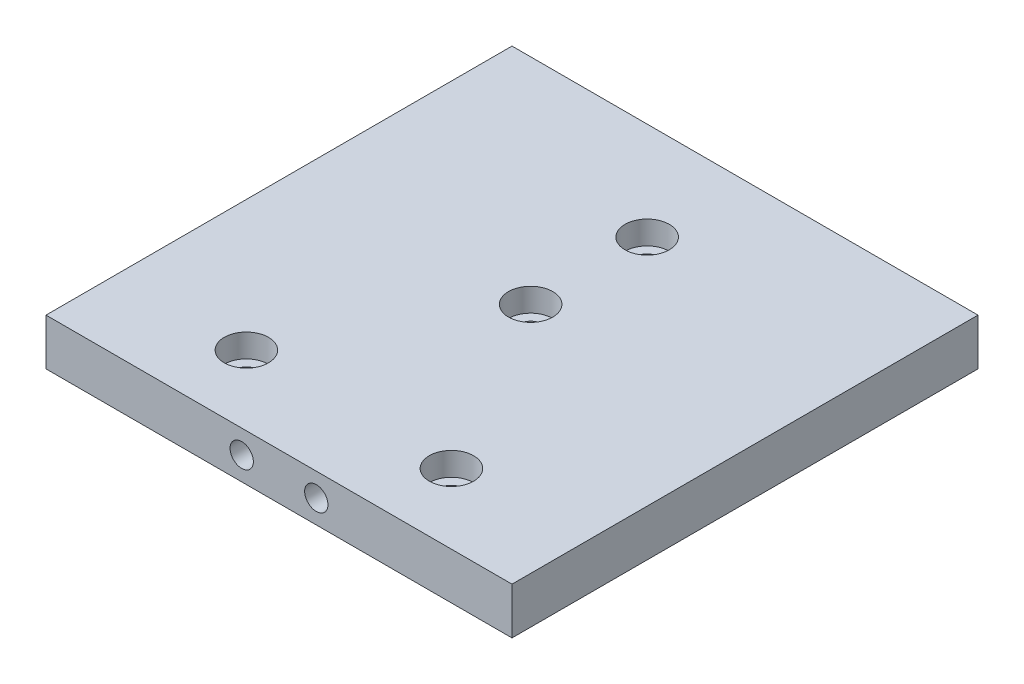
SolidWorks part; units mm, degrees
ref_plane "정면" through (0, 0, 0) normal (0, 0, 1) x (1, 0, 0)
ref_plane "윗면" through (0, 0, 0) normal (0, 1, 0) x (1, 0, 0)
ref_plane "우측면" through (0, 0, 0) normal (1, 0, 0) x (0, 0, -1)
sketch "스케치1" plane through (0, 0, 0) normal (0, 1, 0) x (1, 0, 0)
  line L0 (0, 50) -> (0, -58.2452) construction
  line L1 (-50, -50) -> (50, -50)
  line L2 (-50, -50) -> (-50, 50)
  line L3 (-50, 50) -> (50, 50)
  line L4 (50, -50) -> (50, 50)
  line L5 (-50, -50) -> (50, 50) construction
  line L6 (-50, 50) -> (50, -50) construction
  point P0 (0, 0)
  dimension "D1" = 100
  dimension "D2" = 100
extrude "보스-돌출1" add sketch "스케치1" along normal blind 10 contours L1 L4 L3 L2
sketch "스케치2" plane through (0, 10, 0) normal (0, 1, 0) x (1, 0, 0)
  line L0 (0, 50) -> (0, -58.2452) construction
  line L1 (-50, -50) -> (-50, 50) construction
  line L2 (-50, -50) -> (50, -50) construction
  line L3 (50, -50) -> (50, 50) construction
  circle A0 centre (0, 29) radius 4.75
  circle A1 centre (0, 4) radius 4.75
  circle A2 centre (-22, -35) radius 4.75
  circle A3 centre (22, -35) radius 4.75
  circle A4 centre (0, 29) radius 2.65
  circle A5 centre (0, 4) radius 2.65
  circle A6 centre (-22, -35) radius 2.65
  circle A7 centre (22, -35) radius 2.65
  dimension "D1" = 9.5
  dimension "D2" = 9.5
  dimension "D3" = 9.5
  dimension "D4" = 9.5
  dimension "D5" = 5.3
  dimension "D6" = 5.3
  dimension "D7" = 5.3
  dimension "D8" = 5.3
  dimension "D9" = 28
  dimension "D10" = 15
  dimension "D11" = 15
  dimension "D12" = 28
  dimension "D13" = 54
  dimension "D14" = 79
sketch "스케치3" plane through (0, 0, 50) normal (0, 0, 1) x (1, 0, 0)
  line L0 (0, 0) -> (0, 22.2392) construction
  line L5 (-50, 10) -> (50, 10) construction
  circle A0 centre (-8, 5) radius 2.5
  circle A1 centre (-8, 5) radius 1.5
  circle A2 centre (8, 5) radius 2.5
  circle A3 centre (8, 5) radius 1.5
  dimension "D1" = 5
  dimension "D2" = 3
  dimension "D3" = 5
  dimension "D4" = 3
  dimension "D5" = 8
  dimension "D6" = 8
  dimension "D7" = 5
  dimension "D8" = 5
extrude "컷-돌출1" cut sketch "스케치3" against normal blind 10 contours A0
extrude "컷-돌출2" cut sketch "스케치3<3>" against normal blind 70 contours A1
sketch "스케치3<3>" plane through (0, 0, 50) normal (0, 0, 1) x (1, 0, 0) same geometry as "스케치3"
extrude "컷-돌출3" cut sketch "스케치3<4>" against normal blind 70 contours A3
sketch "스케치3<4>" plane through (0, 0, 50) normal (0, 0, 1) x (1, 0, 0) same geometry as "스케치3"
extrude "컷-돌출4" cut sketch "스케치3<7>" against normal blind 10 contours A2
sketch "스케치3<7>" plane through (0, 0, 50) normal (0, 0, 1) x (1, 0, 0) same geometry as "스케치3"
sketch "스케치4" plane through (0, 0, 0) normal (0, -1, 0) x (1, 0, 0)
  line L0 (-50, 50) -> (50, 50) construction
  line L1 (-50, 50) -> (-50, -50) construction
  line L2 (50, 50) -> (50, -50) construction
  circle A0 centre (-8.0001, 35) radius 1
  circle A1 centre (8, 35) radius 1
  circle A2 centre (8, -16.5) radius 1
  circle A3 centre (-8.0001, -16.5) radius 1
  dimension "D1" = 2
  dimension "D2" = 2
  dimension "D3" = 2
  dimension "D4" = 2
  dimension "D5" = 15
  dimension "D6" = 66.5
  dimension "D7" = 41.9999
  dimension "D8" = 42
  dimension "D9" = 66.5
  dimension "D10" = 42
  dimension "D11" = 41.9999
  dimension "D12" = 15
extrude "컷-돌출5" cut sketch "스케치4" against normal blind 5 contours A0 | A1 | A2 | A3 region at (-8.0001, 0, 35) region at (8, 0, 35) region at (8, 0, -16.5) region at (-8.0001, 0, -16.5)
extrude "컷-돌출6" cut sketch "스케치2" against normal blind 10 contours A6 | A7 | A5 | A4 region at (0, 10, -29) region at (0, 10, -4) region at (-22, 10, 35) region at (22, 10, 35)
extrude "컷-돌출7" cut sketch "스케치2<3>" against normal blind 5 contours A2 A6 | A3 A7 | A1 A5 | A0 A4 region at (-4.6156, 10, -29) region at (-4.6156, 10, -4) region at (-26.6156, 10, 35) region at (17.3844, 10, 35)
sketch "스케치2<3>" plane through (0, 10, 0) normal (0, 1, 0) x (1, 0, 0) same geometry as "스케치2"
